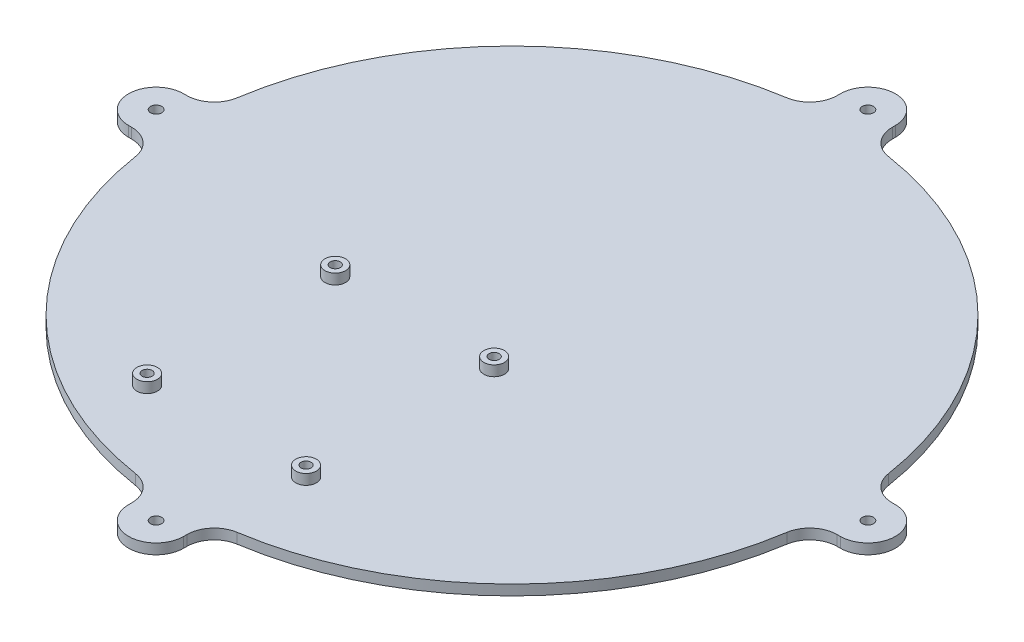
SolidWorks part; units mm, degrees
ref_plane "Front Plane" through (0, 0, 0) normal (0, 0, 1) x (1, 0, 0)
ref_plane "Top Plane" through (0, 0, 0) normal (0, 1, 0) x (1, 0, 0)
ref_plane "Right Plane" through (0, 0, 0) normal (1, 0, 0) x (0, 0, -1)
sketch "Sketch1" plane through (0, 0, 0) normal (0, 1, 0) x (1, 0, 0)
  line L0 (-8.4836, 101.2452) -> (-8.4836, 109.7288)
  line L9 (8.4836, 109.7288) -> (8.4836, 101.2452)
  line L10 (109.7288, -8.4836) -> (101.2452, -8.4836)
  line L11 (101.2452, 8.4836) -> (109.7288, 8.4836)
  line L12 (-8.4836, -109.7288) -> (-8.4836, -101.2452)
  line L13 (8.4836, -101.2452) -> (8.4836, -109.7288)
  line L14 (-109.7288, 8.4836) -> (-101.2452, 8.4836)
  line L15 (-101.2452, -8.4836) -> (-109.7288, -8.4836)
  line L16 (0, 0) -> (0, 146.6167) construction
  circle A1 centre (0, 109.7288) radius 1.7272
  circle A2 centre (109.7288, 0) radius 1.7272
  circle A3 centre (0, -109.7288) radius 1.7272
  circle A4 centre (-109.7288, 0) radius 1.7272
  arc A6 (-8.4836, 101.2452) -> (-101.2452, 8.4836) centre (0, 0) ccw
  arc A10 (101.2452, 8.4836) -> (8.4836, 101.2452) centre (0, 0) ccw
  arc A11 (8.4836, -101.2452) -> (101.2452, -8.4836) centre (0, 0) ccw
  arc A12 (-101.2452, -8.4836) -> (-8.4836, -101.2452) centre (0, 0) ccw
  arc A13 (8.4836, 109.7288) -> (-8.4836, 109.7288) centre (0, 109.7288) ccw
  arc A14 (109.7288, -8.4836) -> (109.7288, 8.4836) centre (109.7288, 0) ccw
  arc A15 (-8.4836, -109.7288) -> (8.4836, -109.7288) centre (0, -109.7288) ccw
  arc A16 (-109.7288, 8.4836) -> (-109.7288, -8.4836) centre (-109.7288, 0) ccw
  point P17 (0, 0)
  point P36 (0, 0)
  point P44 (0, 0)
  dimension "D1" = 4
  dimension "D2" = 3.4544
  dimension "D4" = 4
  dimension "D5" = 8.4836
  dimension "D6" = 0
  dimension "D9" = 203.2
  dimension "D3" = 16.9672
extrude "Boss-Extrude1" add sketch "Sketch1" along normal blind 3.175
fillet "Fillet2" radius 8.4836 8 edges at (-8.4836, 1.5875, -101.2452) (8.4836, 1.5875, -101.2452) (101.2452, 1.5875, -8.4836) (101.2452, 1.5875, 8.4836) (8.4836, 1.5875, 101.2452) (-8.4836, 1.5875, 101.2452) (-101.2452, 1.5875, -8.4836) (-101.2452, 1.5875, 8.4836)
sketch "Sketch2" plane through (0, 3.175, 0) normal (0, 1, 0) x (1, 0, 0)
  line L1 (-15.6596, -100.3859) -> (15.6596, -100.3859) construction
  line L2 (11.4859, -74.9859) -> (-37.5141, -74.9859) construction
  line L3 (-37.5141, -74.9859) -> (-37.5141, -16.9859) construction
  line L4 (-37.5141, -16.9859) -> (11.4859, -16.9859) construction
  line L5 (11.4859, -16.9859) -> (11.4859, -74.9859) construction
  circle A1 centre (-37.5141, -74.9859) radius 3.175
  circle A2 centre (-37.5141, -16.9859) radius 3.175
  circle A4 centre (11.4859, -74.9859) radius 3.175
  circle A5 centre (11.4859, -16.9859) radius 3.175
  dimension "D1" = 6.35
  dimension "D2" = 49
  dimension "D4" = 6.35
  dimension "D5" = 58
  dimension "D6" = 6.35
  dimension "D7" = 6.35
  dimension "D8" = 88.9
  dimension "D3" = 50.8
extrude "Boss-Extrude2" add sketch "Sketch2" along normal blind 3.175
hole_wizard "CSK for M2.5 Cross Countersunk Head Screw4" positions "Sketch6" profile "Sketch7" countersink size "M2.5" standard "AS" end condition through all
sketch "Sketch6" plane through (0, 0, 0) normal (0, -1, 0) x (-1, 0, 0)
  point P0 (-11.4859, -16.9859)
  point P3 (37.5141, -16.9859)
  point P6 (37.5141, -74.9859)
  point P9 (-11.4859, -74.9859)
sketch "Sketch7" plane through (11.4859, 0, 16.9859) normal (1, 0, 0) x (0, 0, -1)
  line L0 (0, 0) -> (0, 6.35)
  line L1 (0, 6.35) -> (1.55, 6.35)
  line L2 (1.55, 6.35) -> (1.55, 0.9174)
  line L3 (1.55, 0.9174) -> (2.5, 0)
  line L5 (2.5, 0) -> (0, 0)
  line L6 (-1.55, 0.9174) -> (-2.5, 0) construction
  line L11 (0, -6.35) -> (0, 107.95) construction
  dimension "Thru Hole Dia." = 3.1
  dimension "Thru Hole Depth" = 6.35
  dimension "Near C'Sink Dia." = 5
  dimension "Near C'Sink Angle" = 92
